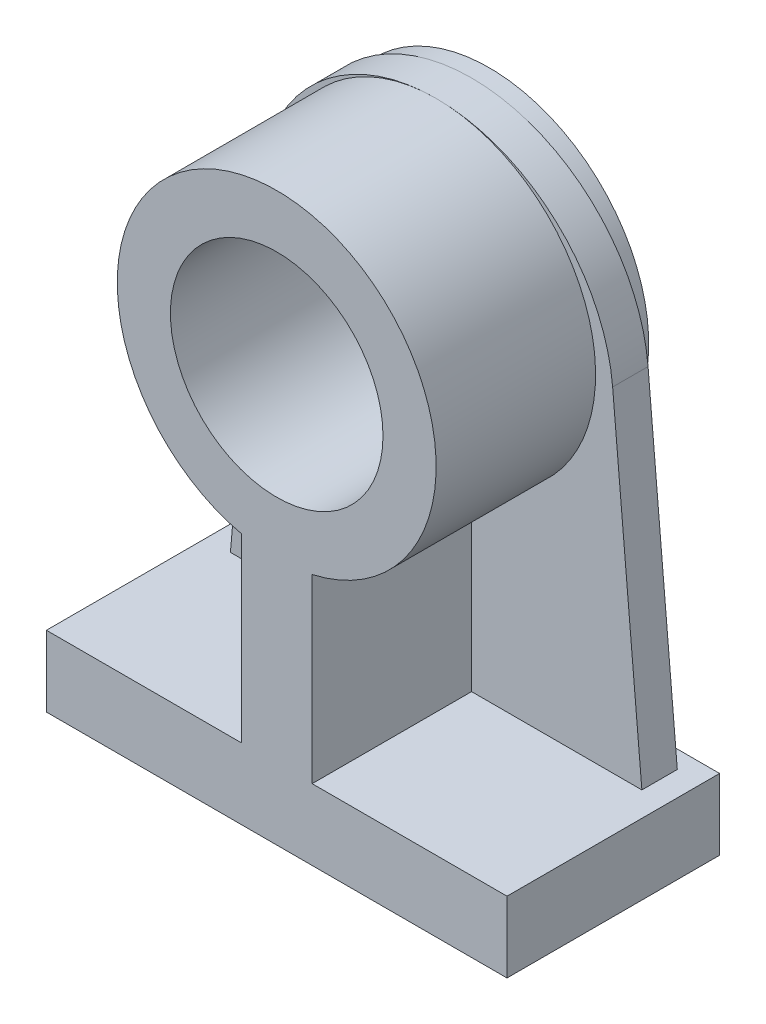
SolidWorks part; units mm, degrees
ref_plane "Přední rovina" through (0, 0, 0) normal (0, 0, 1) x (1, 0, 0)
ref_plane "Vrchní rovina" through (0, 0, 0) normal (0, 1, 0) x (1, 0, 0)
ref_plane "Pravá rovina" through (0, 0, 0) normal (1, 0, 0) x (0, 0, -1)
sketch "Skica1" plane through (0, 0, 0) normal (0, 0, 1) x (1, 0, 0)
  line L0 (0, -9.8974) -> (0, 80.1984) construction
  line L1 (-5, 30.5626) -> (-5, 5)
  line L2 (-32.5, 5) -> (-5, 5)
  line L3 (-32.5, 5) -> (-32.5, -5)
  line L4 (-32.5, -5) -> (32.5, -5)
  line L5 (32.5, 5) -> (32.5, -5)
  line L6 (-32.5, 5) -> (32.5, -5) construction
  line L7 (-32.5, -5) -> (32.5, 5) construction
  line L8 (5, 30.5626) -> (5, 5)
  line L9 (5, 5) -> (32.5, 5)
  line L10 (-33.8199, 52.5) -> (34.5063, 52.5) construction
  line L11 (29.0325, 5) -> (24.9049, 52.1789)
  line L12 (-29.0325, 5) -> (-24.9049, 52.1789)
  circle A0 centre (0, 52.5) radius 15
  arc A1 (5, 30.5626) -> (-5, 30.5626) centre (0, 52.5) ccw
  arc A2 (-24.9049, 52.1789) -> (24.9049, 52.1789) centre (0, 50) cw
  point P5 (0, 0)
  point P6 (0, 0)
  point P15 (0, 0)
  point P22 (0, 0)
  point P23 (0, 0)
  point P24 (-28.2857, 5)
  dimension "D1" = 45
  dimension "D2" = 30
  dimension "D8" = 85
  dimension "D7" = 25
  dimension "D3" = 65
  dimension "D4" = 10
  dimension "D5" = 80
  dimension "D6" = 10
extrude "Přidat vysunutím1" add sketch "Skica1" along normal mid plane 5 contours L8 A1 L1 L2 L3 L4 L5 L9 A0 | A2 L12 L2 L1 A1 | A2 A1 L8 L9 L11 region at (0, 28.463, 0) region at (-17.5323, 23.6372, 0) region at (17.5323, 23.6372, 0)
extrude "Přidat vysunutím2" add sketch "Skica1<3>" along normal blind 25 and the other way blind 5 contours L8 A1 L1 L2 L3 L4 L5 L9 A0 region at (0, 28.463, 0)
sketch "Skica1<3>" plane through (0, 0, 0) normal (0, 0, 1) x (1, 0, 0) same geometry as "Skica1"
